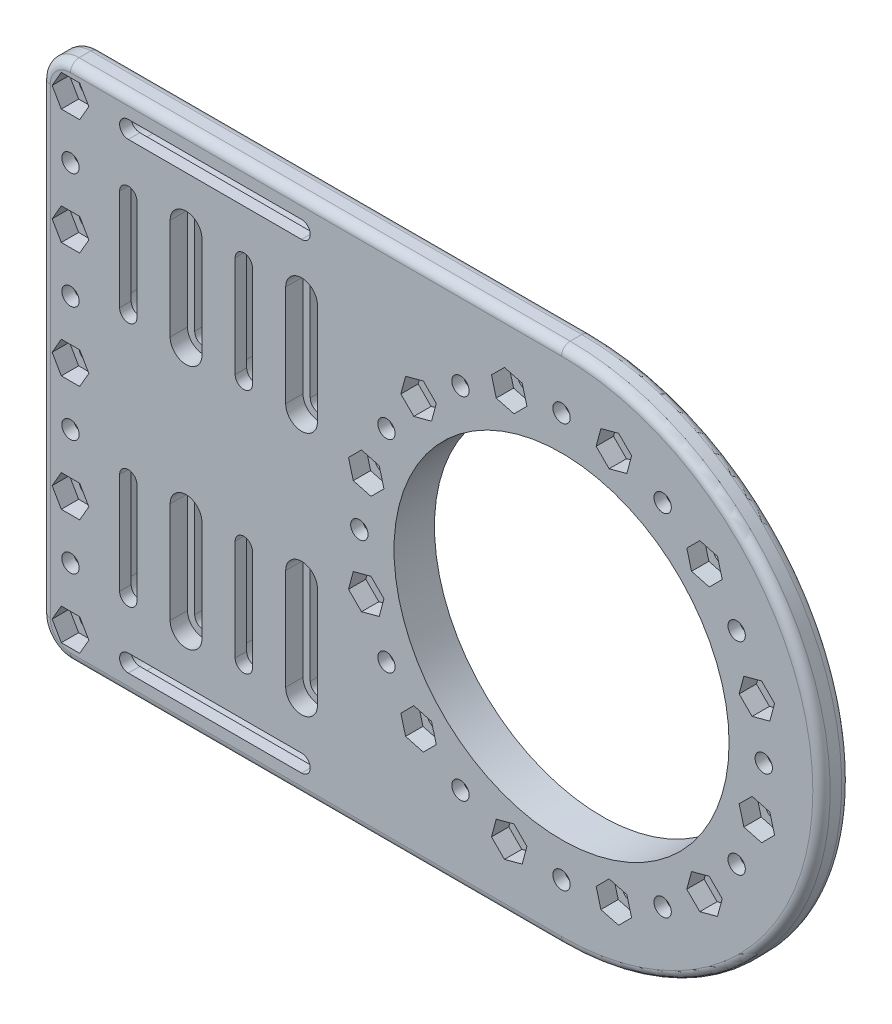
SolidWorks part; units mm, degrees
ref_plane "前视基准面" through (0, 0, 0) normal (0, 0, 1) x (1, 0, 0)
ref_plane "上视基准面" through (0, 0, 0) normal (0, 1, 0) x (1, 0, 0)
ref_plane "右视基准面" through (0, 0, 0) normal (1, 0, 0) x (0, 0, -1)
other "Configuration Table"
sketch "草图1" plane through (0, 0, 0) normal (0, 0, 1) x (1, 0, 0)
  line L1 (-45, -45) -> (45, -45)
  line L2 (-45, -45) -> (-45, 45)
  line L3 (-45, 45) -> (45, 45)
  line L4 (45, -45) -> (45, 45) construction
  line L5 (-45, -45) -> (45, 45) construction
  line L6 (-45, 45) -> (45, -45) construction
  arc A0 (45, -45) -> (45, 45) centre (45, 0) ccw
  point P0 (0, 0)
  dimension "D1" = 90
  dimension "D2" = 90
extrude "凸台-拉伸1" add sketch "草图1" along normal blind 5
sketch "草图2" plane through (0, 0, 5) normal (0, 0, 1) x (1, 0, 0)
  circle A0 centre (45, 0) radius 29
  dimension "D1" = 58
extrude "切除-拉伸1" cut sketch "草图2" against normal through all
sketch "草图3" plane through (0, 0, 0) normal (0, 0, 1) x (1, 0, 0)
  circle A0 centre (45, 0) radius 29
  circle A1 centre (45, 0) radius 45
  circle A2 centre (45, 0) radius 29 construction
  dimension "D1" = 90
extrude "凸台-拉伸2" add sketch "草图3" against normal blind 2
sketch "草图9" plane through (0, 0, -2) normal (0, 0, -1) x (-1, 0, 0)
  circle A0 centre (-45, 0) radius 45
  circle A1 centre (-45, 0) radius 31
  dimension "D1" = 62
extrude "切除-拉伸10" cut sketch "草图9" against normal blind 2
sketch "草图5" plane through (0, 0, 0) normal (0, 0, -1) x (-1, 0, 0)
  line L1 (-45, 35) -> (-45, 0) construction
  circle A0 centre (-45, 0) radius 35 construction
  circle A1 centre (-45, 35) radius 1.5
  dimension "D1" = 3
  dimension "D2" = 70
extrude "切除-拉伸2" cut sketch "草图5" against normal through all
sketch "草图6" plane through (0, 0, 0) normal (0, 0, -1) x (-1, 0, 0)
  line L0 (-45, 35) -> (-45, 0) construction
  line L1 (-45, 31.8246) -> (-42.25, 33.4123)
  line L2 (-42.25, 33.4123) -> (-42.25, 36.5877)
  line L3 (-42.25, 36.5877) -> (-45, 38.1754)
  line L4 (-45, 38.1754) -> (-47.75, 36.5877)
  line L5 (-47.75, 36.5877) -> (-47.75, 33.4123)
  line L6 (-47.75, 33.4123) -> (-45, 31.8246)
  circle A1 centre (-45, 35) radius 2.75 construction
  dimension "D1" = 5.5
extrude "切除-拉伸3" cut sketch "草图6" against normal blind 3
sketch "草图10" plane through (0, 0, -2) normal (0, 0, -1) x (-1, 0, 0)
  line L0 (-45, 0) -> (-35.9413, 33.8074) construction
  line L1 (-45, -1000) -> (-45, 49000) construction
  circle A0 centre (-35.9413, 33.8074) radius 1.5
  circle A1 centre (-45, 0) radius 35 construction
  dimension "D1" = 3
  dimension "D2" = 15
extrude "切除-拉伸11" cut sketch "草图10" against normal through all
sketch "草图11" plane through (0, 0, 5) normal (0, 0, 1) x (1, 0, 0)
  line L0 (35.9413, 33.8074) -> (45, 0) construction
  line L1 (36.7632, 30.7402) -> (39.0086, 32.9855)
  line L2 (39.0086, 32.9855) -> (38.1867, 36.0528)
  line L3 (38.1867, 36.0528) -> (35.1195, 36.8746)
  line L4 (35.1195, 36.8746) -> (32.8741, 34.6293)
  line L5 (32.8741, 34.6293) -> (33.696, 31.562)
  line L6 (33.696, 31.562) -> (36.7632, 30.7402)
  circle A0 centre (35.9413, 33.8074) radius 2.75 construction
  dimension "D1" = 5.5
extrude "切除-拉伸12" cut sketch "草图11" against normal blind 3
pattern_circular "阵列(圆周)1" count 12 over 360 about axis through (45, 0, 0) along (0, 0, 1) of "切除-拉伸3", "切除-拉伸2", "切除-拉伸11", "切除-拉伸12", "切除-拉伸1"
sketch "草图7" plane through (0, 0, 5) normal (0, 0, 1) x (1, 0, 0)
  line L0 (-30, 40) -> (0, 40) construction
  line L1 (-30, 41.5) -> (0, 41.5)
  line L2 (-30, 38.5) -> (0, 38.5)
  line L3 (-1000, 0) -> (49000, 0) construction
  line L4 (-30, -40) -> (0, -40) construction
  line L7 (-30, -41.5) -> (0, -41.5)
  line L8 (-30, -38.5) -> (0, -38.5)
  line L9 (-45, 45) -> (-45, -45) construction
  arc A0 (-30, 41.5) -> (-30, 38.5) centre (-30, 40) ccw
  arc A1 (0, 38.5) -> (0, 41.5) centre (0, 40) ccw
  arc A4 (-30, -41.5) -> (-30, -38.5) centre (-30, -40) cw
  arc A5 (0, -38.5) -> (0, -41.5) centre (0, -40) cw
  point P2 (-15, 40)
  point P12 (-15, -40)
  dimension "D1" = 3
  dimension "D2" = 80
  dimension "D3" = 15
  dimension "D4" = 30
sketch "草图8" plane through (0, 0, 0) normal (0, 0, 1) x (1, 0, 0)
  line L0 (-30, 40) -> (0, 40) construction
  line L1 (-30, 42.75) -> (0, 42.75)
  line L2 (-30, 37.25) -> (0, 37.25)
  line L3 (-30, -40) -> (0, -40) construction
  line L4 (-30, -37.25) -> (0, -37.25)
  line L5 (-30, -42.75) -> (0, -42.75)
  arc A0 (-30, 42.75) -> (-30, 37.25) centre (-30, 40) ccw
  arc A1 (0, 37.25) -> (0, 42.75) centre (0, 40) ccw
  arc A2 (-30, -37.25) -> (-30, -42.75) centre (-30, -40) ccw
  arc A3 (0, -42.75) -> (0, -37.25) centre (0, -40) ccw
  point P4 (-15, 40)
  point P13 (-15, -40)
  dimension "D1" = 5.5
  dimension "D2" = 5.5
extrude "切除-拉伸7" cut sketch "草图7" against normal through all
extrude "切除-拉伸9" cut sketch "草图8" along normal blind 3
sketch "草图12" plane through (0, 0, 5) normal (0, 0, 1) x (1, 0, 0)
  line L0 (-45, 45) -> (-45, -45) construction
  circle A0 centre (-40, 0) radius 1.5
  dimension "D2" = 3
  dimension "D1" = 5
sketch "草图13" plane through (0, 0, 5) normal (0, 0, 1) x (1, 0, 0)
  line L1 (-36.8246, 0) -> (-38.4123, 2.75)
  line L2 (-38.4123, 2.75) -> (-41.5877, 2.75)
  line L3 (-41.5877, 2.75) -> (-43.1754, 0)
  line L4 (-43.1754, 0) -> (-41.5877, -2.75)
  line L5 (-41.5877, -2.75) -> (-38.4123, -2.75)
  line L6 (-38.4123, -2.75) -> (-36.8246, 0)
  circle A1 centre (-40, 0) radius 2.75 construction
  dimension "D1" = 5.5
extrude "切除-拉伸13" cut sketch "草图12" against normal through all
extrude "切除-拉伸14" cut sketch "草图13" against normal blind 3
pattern_linear "阵列(线性)5" count 5 spacing 10 along (0, -1, 0) count 5 spacing 10 along (0, 1, 0) of "切除-拉伸13"
pattern_linear "阵列(线性)1" count 3 spacing 20 along (0, -1, 0) count 3 spacing 20 along (0, 1, 0) of "切除-拉伸14"
sketch "草图14" plane through (0, 0, 5) normal (0, 0, 1) x (1, 0, 0)
  line L0 (0, 30) -> (0, 12.5) construction
  line L1 (1.5, 30) -> (1.5, 12.5)
  line L2 (-1.5, 30) -> (-1.5, 12.5)
  line L3 (-1000, 0) -> (49000, 0) construction
  line L4 (0, -30) -> (0, -12.5) construction
  line L5 (1.5, -30) -> (1.5, -12.5)
  line L6 (-1.5, -30) -> (-1.5, -12.5)
  arc A0 (1.5, 30) -> (-1.5, 30) centre (0, 30) ccw
  arc A1 (-1.5, 12.5) -> (1.5, 12.5) centre (0, 12.5) ccw
  arc A2 (1.5, -30) -> (-1.5, -30) centre (0, -30) cw
  arc A3 (-1.5, -12.5) -> (1.5, -12.5) centre (0, -12.5) cw
  circle A4 centre (45, 0) radius 45 construction
  point P2 (0, 21.25)
  point P12 (0, -21.25)
  dimension "D1" = 3
  dimension "D2" = 30
  dimension "D3" = 25
  dimension "D4" = 0
sketch "草图15" plane through (0, 0, 5) normal (0, 0, 1) x (1, 0, 0)
  line L0 (0, 12.5) -> (0, 30) construction
  line L1 (-2.75, 12.5) -> (-2.75, 30)
  line L2 (2.75, 12.5) -> (2.75, 30)
  line L3 (0, -12.5) -> (0, -30) construction
  line L4 (2.75, -12.5) -> (2.75, -30)
  line L5 (-2.75, -12.5) -> (-2.75, -30)
  arc A0 (-2.75, 12.5) -> (2.75, 12.5) centre (0, 12.5) ccw
  arc A1 (2.75, 30) -> (-2.75, 30) centre (0, 30) ccw
  arc A2 (2.75, -12.5) -> (-2.75, -12.5) centre (0, -12.5) ccw
  arc A3 (-2.75, -30) -> (2.75, -30) centre (0, -30) ccw
  point P4 (0, 21.25)
  point P9 (0, -21.25)
  dimension "D1" = 5.5
  dimension "D2" = 5.5
sketch "草图17" plane through (0, 0, 0) normal (0, 0, -1) x (-1, 0, 0)
  line L1 (43.1754, 10) -> (41.5877, 12.75)
  line L2 (41.5877, 12.75) -> (38.4123, 12.75)
  line L3 (38.4123, 12.75) -> (36.8246, 10)
  line L4 (36.8246, 10) -> (38.4123, 7.25)
  line L5 (38.4123, 7.25) -> (41.5877, 7.25)
  line L6 (41.5877, 7.25) -> (43.1754, 10)
  circle A0 centre (40, 10) radius 2.75 construction
  dimension "D1" = 5.5
extrude "切除-拉伸18" cut sketch "草图17" against normal blind 3
pattern_linear "阵列(线性)6" count 3 spacing 20 along (0, -1, 0) count 3 spacing 20 along (0, 1, 0) of "切除-拉伸18"
extrude "切除-拉伸15" cut sketch "草图14" against normal through all
extrude "切除-拉伸16" cut sketch "草图15" against normal blind 3
pattern_linear "阵列(线性)2" count 4 spacing 10 along (-1, 0, 0) of "切除-拉伸15"
pattern_linear "阵列(线性)3" count 2 spacing 20 along (-1, 0, 0) of "切除-拉伸16"
sketch "草图16" plane through (0, 0, 0) normal (0, 0, -1) x (-1, 0, 0)
  line L0 (30, 30) -> (30, 12.5) construction
  line L3 (32.75, 30) -> (32.75, 12.5)
  line L6 (27.25, 30) -> (27.25, 12.5)
  line L7 (30, -12.5) -> (30, -30) construction
  line L8 (32.75, -12.5) -> (32.75, -30)
  line L9 (27.25, -12.5) -> (27.25, -30)
  arc A4 (32.75, 30) -> (27.25, 30) centre (30, 30) ccw
  arc A5 (27.25, 12.5) -> (32.75, 12.5) centre (30, 12.5) ccw
  arc A6 (32.75, -12.5) -> (27.25, -12.5) centre (30, -12.5) ccw
  arc A7 (27.25, -30) -> (32.75, -30) centre (30, -30) ccw
  point P4 (30, 21.25)
  point P9 (30, -21.25)
  dimension "D1" = 5.5
  dimension "D2" = 5.5
extrude "切除-拉伸17" cut sketch "草图16" against normal blind 3
pattern_linear "阵列(线性)4" count 2 spacing 20 along (1, 0, 0) of "切除-拉伸17"
fillet "圆角4" radius 1.5 8 edges at (0, -45, 5) (0, -45, 0) (90, 0, 0) (0, 45, 5) (0, 45, 0) (90, 0, 5) (-45, 0, 5) (-45, 0, 0)
fillet "圆角5" radius 5 6 edges at (-44.5607, -44.5607, 0.4393) (-44.5607, -44.5607, 4.5607) (-44.5607, 44.5607, 0.4393) (-44.5607, 44.5607, 4.5607) (-45, 45, 2.5) (-45, -45, 2.5)
